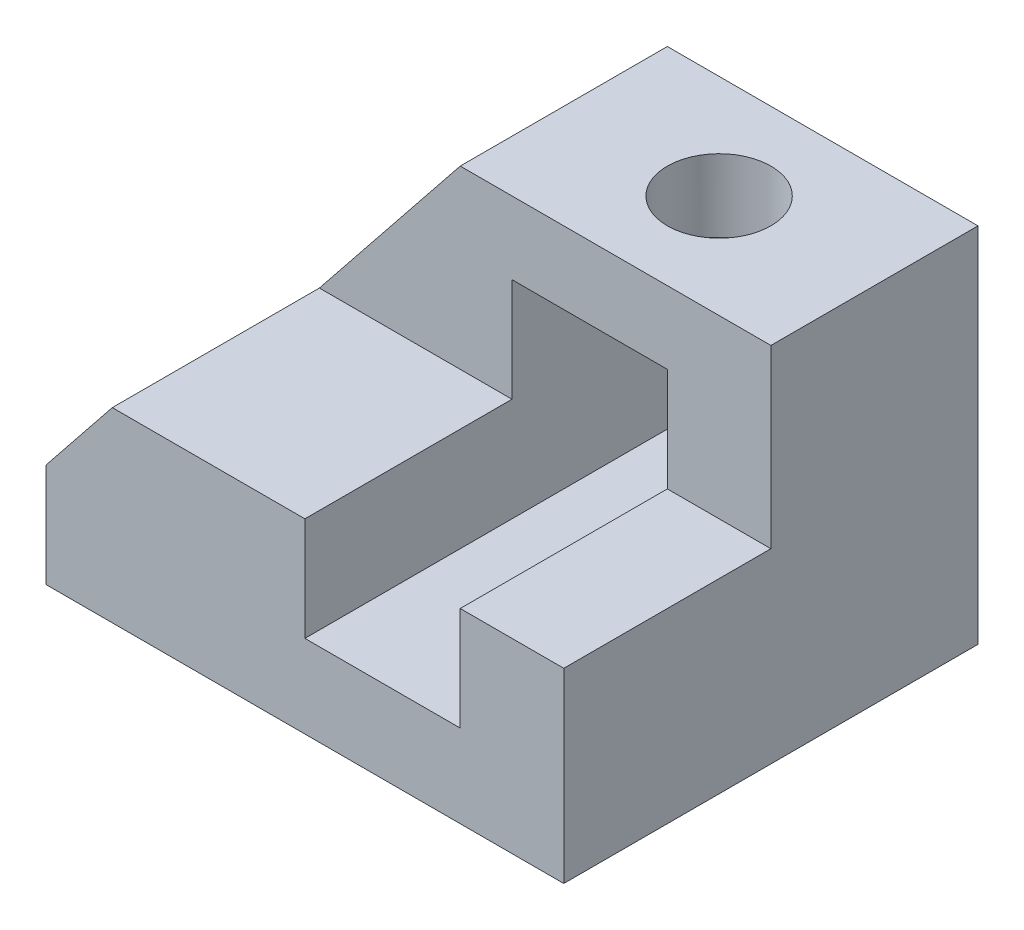
SolidWorks part; units mm, degrees
ref_plane "Front Plane" through (0, 0, 0) normal (0, 0, 1) x (1, 0, 0)
ref_plane "Top Plane" through (0, 0, 0) normal (0, 1, 0) x (1, 0, 0)
ref_plane "Right Plane" through (0, 0, 0) normal (1, 0, 0) x (0, 0, -1)
sketch "Sketch2" plane through (0, 0, 0) normal (0, 0, 1) x (1, 0, 0)
  line L0 (0, 0) -> (0, 10)
  line L1 (20, 35) -> (50, 35)
  line L2 (50, 35) -> (50, 0)
  line L3 (50, 0) -> (0, 0)
  line L4 (0, 10) -> (20, 35)
  line L5 (6.4, 18) -> (50, 18)
  line L6 (25, 18) -> (25, 28)
  line L7 (25, 28) -> (40, 28)
  line L8 (40, 28) -> (40, 18)
  line L9 (40, 18) -> (40, 8)
  line L10 (40, 8) -> (25, 8)
  line L11 (25, 8) -> (25, 18)
  dimension "D1" = 50
  dimension "D2" = 35
  dimension "D3" = 20
  dimension "D4" = 10
  dimension "D5" = 18
  dimension "D6" = 15
  dimension "D7" = 25
  dimension "D8" = 20
  dimension "D9" = 8
extrude "Boss-Extrude1" add sketch "Sketch2" along normal blind 40 contours L10 L11 L5 L4 L0 L3 L2 L9 region at (24.2551, 7.9479, 0)
extrude "Boss-Extrude2" add sketch "Sketch2<4>" along normal blind 20 contours L7 L8 L5 L2 L1 L4 L6 region at (13.5654, 26.2077, 0)
sketch "Sketch2<4>" plane through (0, 0, 0) normal (0, 0, 1) x (1, 0, 0) same geometry as "Sketch2"
sketch "Sketch4" plane through (0, 35, 0) normal (0, 1, 0) x (1, 0, 0)
  line L4 (50, 0) -> (20, 0)
  line L5 (20, 0) -> (20, -20)
  line L6 (20, -20) -> (50, -20)
  line L7 (50, -20) -> (50, 0)
  line L8 (50, 0) -> (20, 0)
  line L9 (20, 0) -> (20, -20)
  line L10 (20, -20) -> (50, -20)
  line L11 (50, -20) -> (50, 0)
  circle A0 centre (35, -10) radius 5
  dimension "D2" = 10
  dimension "D3" = 15
  dimension "D4" = 10
  dimension "D1" = 0
extrude "Cut-Extrude3" cut sketch "Sketch4" against normal blind 20 contours A0
